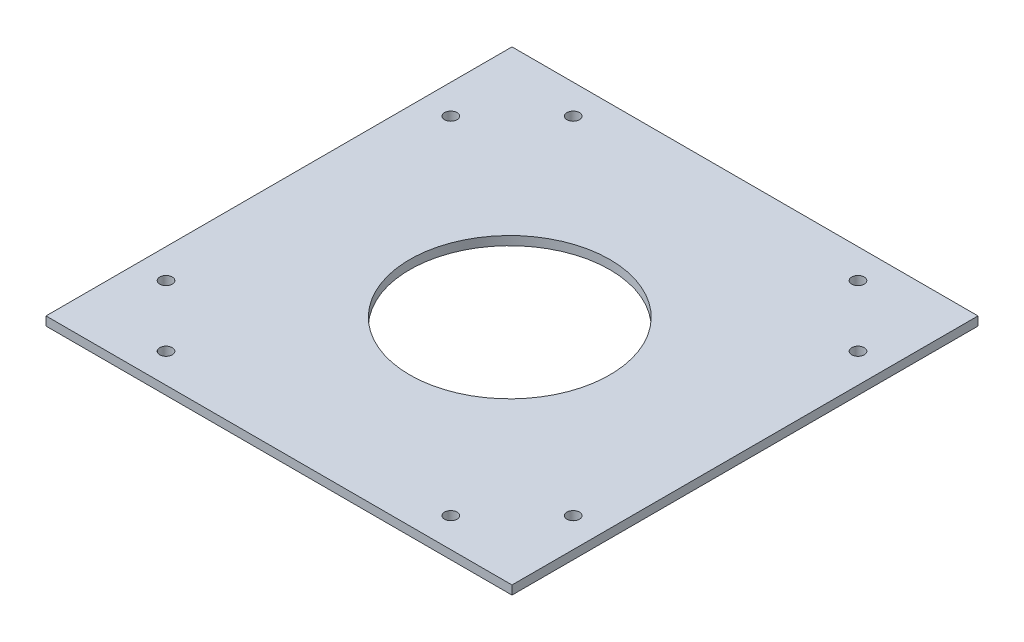
SolidWorks part; units mm, degrees
ref_plane "Front Plane" through (0, 0, 0) normal (0, 0, 1) x (1, 0, 0)
ref_plane "Top Plane" through (0, 0, 0) normal (0, 1, 0) x (1, 0, 0)
ref_plane "Right Plane" through (0, 0, 0) normal (1, 0, 0) x (0, 0, -1)
sketch "Sketch1" plane through (0, 0, 0) normal (0, 1, 0) x (1, 0, 0)
  line L1 (-79.2, -79.2) -> (79.2, -79.2)
  line L2 (-79.2, -79.2) -> (-79.2, 79.2)
  line L3 (-79.2, 79.2) -> (79.2, 79.2)
  line L4 (79.2, -79.2) -> (79.2, 79.2)
  line L5 (-79.2, -79.2) -> (79.2, 79.2) construction
  line L6 (-79.2, 79.2) -> (79.2, -79.2) construction
  point P0 (0, 0)
  dimension "D1" = 158.4
  dimension "D2" = 158.4
extrude "Boss-Extrude1" add sketch "Sketch1" along normal blind 3
sketch "Sketch2" plane through (0, 3, 0) normal (0, 1, 0) x (1, 0, 0)
  line L0 (79.2, 79.2) -> (59.2, 79.2) construction
  line L1 (-79.2, 79.2) -> (-59.2, 79.2) construction
  line L2 (-79.2, 79.2) -> (-79.2, 59.2) construction
  line L3 (-79.2, 59.2) -> (-59.2, 59.2) construction
  line L4 (-59.2, 79.2) -> (-59.2, 59.2) construction
  line L5 (79.2, 79.2) -> (79.2, 59.2) construction
  line L6 (79.2, 59.2) -> (59.2, 59.2) construction
  line L7 (59.2, 79.2) -> (59.2, 59.2) construction
  line L8 (79.2, -79.2) -> (79.2, -59.2) construction
  line L9 (79.2, -79.2) -> (59.2, -79.2) construction
  line L10 (59.2, -79.2) -> (59.2, -59.2) construction
  line L11 (79.2, -59.2) -> (59.2, -59.2) construction
  line L12 (-79.2, -79.2) -> (-59.2, -79.2) construction
  line L13 (-79.2, -79.2) -> (-79.2, -59.2) construction
  line L14 (-79.2, -59.2) -> (-59.2, -59.2) construction
  line L15 (-59.2, -79.2) -> (-59.2, -59.2) construction
  line L16 (-69.2, -79.2) -> (-69.2, 79.2) construction
  line L17 (-79.2, 0) -> (79.2, 0) construction
  line L18 (-79.2, 79.2) -> (-79.2, -79.2) construction
  line L19 (79.2, -79.2) -> (79.2, 79.2) construction
  circle A0 centre (-69.2, -48.4) radius 2.125
  circle A1 centre (-69.2, 48.4) radius 2.125
  circle A2 centre (-48.4, 69.2) radius 2.125
  circle A3 centre (48.4, 69.2) radius 2.125
  circle A4 centre (69.2, 48.4) radius 2.125
  circle A5 centre (69.2, -48.4) radius 2.125
  circle A6 centre (48.4, -69.2) radius 2.125
  circle A7 centre (-48.4, -69.2) radius 2.125
  circle A8 centre (0, -0.7554) radius 34
  point P44 (0, 0)
  dimension "D4" = 4.25
  dimension "D7" = 68
  dimension "D1" = 20
  dimension "D2" = 20
  dimension "D5" = 10.8
  dimension "D3" = 4
  dimension "D6" = 4
extrude "Cut-Extrude3" cut sketch "Sketch2" against normal through all
